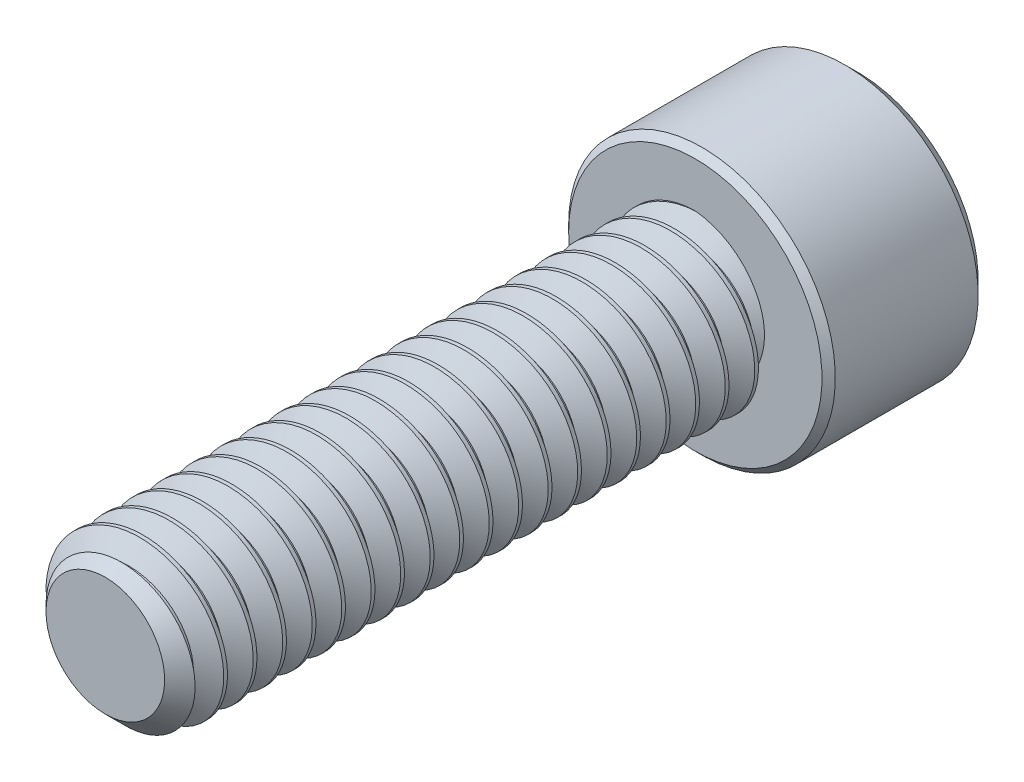
SolidWorks part; units mm, degrees
ref_plane "Front Plane" through (0, 0, 0) normal (0, 0, 1) x (1, 0, 0)
ref_plane "Top Plane" through (0, 0, 0) normal (0, 1, 0) x (1, 0, 0)
ref_plane "Right Plane" through (0, 0, 0) normal (1, 0, 0) x (0, 0, -1)
sketch "Sketch0" plane through (0, 0, 0) normal (1, 0, 0) x (0, 0, -1)
  line L0 (0, 0) -> (12.7, 0) construction
  point P2 (16.2052, 0)
  point P4 (0, 0)
  dimension "D1" = 12.7
  dimension "D2" = 3.5052
  dimension "Min Thread" = 0
sketch "Sketch1" plane through (0, 0, 0) normal (0, 0, 1) x (1, 0, 0)
  circle A0 centre (0, 0) radius 1.7526
  dimension "OD" = 3.5052
extrude "Extrude1" add sketch "Sketch1" against normal blind 12.7
sketch "Sketch2" plane through (0, 0, 0) normal (0, 0, 1) x (1, 0, 0)
  circle A0 centre (0, 0) radius 1.7526 construction
  circle A1 centre (0, 0) radius 1.7526
curve "Helix/Spiral1" pitch 0.635 height 13.335 turns 21 parameters "pitch"=0.635
chamfer "Chamfer3" distance 0.4763 angle 45 1 edges at (1.7526, 0, 0)
sketch "Sketch3" plane through (0, 0, 0) normal (1, 0, 0) x (0, 0, -1)
  line L0 (-0.5556, 1.7526) -> (-0.3175, 1.3402)
  line L1 (-0.3175, 1.3402) -> (-0.2381, 1.3402)
  line L2 (-0.2381, 1.3402) -> (0, 1.7526)
  line L3 (-0.5556, 1.7526) -> (0, 1.7526)
  line L4 (-0.2778, 1.7526) -> (-0.2778, 1.3402) construction
  line L5 (-0.4366, 1.5464) -> (-0.1191, 1.5464) construction
  line L6 (0, 1.7526) -> (0, -1.7526) construction
  dimension "D1" = 0.0794
  dimension "D2" = 0.3175
  dimension "D3" = 60
sweep "Cut-Sweep1" cut profiles "Sketch3" path "Helix/Spiral1"
sketch "Sketch5" plane through (0, 0, 0) normal (1, 0, 0) x (0, 0, -1)
  line L0 (12.7, -1.35) -> (12.7, 1.2505) construction
  line L1 (12.7, 1.7526) -> (0, 1.7526)
  line L2 (12.7, 1.7526) -> (12.7, 0)
  line L3 (12.7, 0) -> (-0.6379, 0)
  line L4 (0, 0) -> (12.7, 0) construction
  line L5 (0, 1.7526) -> (-0.6379, 0)
  line L6 (0, 0) -> (15.24, 0) construction
  dimension "D1" = 70
  dimension "D3" = 2.54
revolve "partially thread" [suppressed] add sketch "Sketch5" angle 360 about L6
sketch "Sketch6" plane through (0, 0, -12.7) normal (0, 0, -1) x (-1, 0, 0)
  circle A0 centre (0, 0) radius 2.8702
  dimension "head dia" = 5.7404
extrude "Extrude2" add sketch "Sketch6" along normal blind 3.5052
sketch "Sketch7" plane through (0, 0, -16.2052) normal (0, 0, -1) x (-1, 0, 0)
  line L1 (0, 1.604) -> (-1.3891, 0.802)
  line L2 (-1.3891, 0.802) -> (-1.3891, -0.802)
  line L3 (-1.3891, -0.802) -> (0, -1.604)
  line L4 (0, -1.604) -> (1.3891, -0.802)
  line L5 (1.3891, -0.802) -> (1.3891, 0.802)
  line L6 (1.3891, 0.802) -> (0, 1.604)
  circle A0 centre (0, 0) radius 1.3891 construction
  dimension "hex dia" = 2.7781
extrude "Cut-Extrude1" cut sketch "Sketch7" against normal blind 2.0836
sketch "Sketch8" plane through (0, 0, -16.2052) normal (0, 0, -1) x (-1, 0, 0)
  circle A0 centre (0, 0) radius 1.604
extrude "Cut-Extrude2" cut sketch "Sketch8" against normal through all draft 45
chamfer "Chamfer1" distance 0.287 angle 45 1 edges at (-2.8702, 0, -16.2052)
chamfer "Chamfer2" distance 0.1435 angle 45 1 edges at (-2.8702, 0, -12.7)
sketch "Sketch9" plane through (0, 0, 0) normal (1, 0, 0) x (0, 0, -1)
  line L0 (0, 1.7526) -> (0, -1.7526) construction
  line L1 (1.5875, 1.7526) -> (1.5875, -1.7526) construction
  line L2 (16.2052, 2.8702) -> (16.2052, -2.8702) construction
  line L3 (12.7, 2.8702) -> (12.7, -2.8702) construction
  line L4 (12.7, 2.7267) -> (12.7, -2.7267) construction
  line L5 (16.2052, -2.5832) -> (16.2052, 2.5832) construction
  line L6 (12.7, -2.8702) -> (12.7, 2.8702) construction
  line L7 (0, 1.2764) -> (0, -1.2764) construction
  line L8 (-0.5556, 1.7526) -> (0, 1.7526) construction
  line L9 (1.5875, 0) -> (0, 0) construction
  dimension "D1" = 1.5875
equation "\"D3@Helix/Spiral1\" = \"screw length@Extrude1\"+\"pitch@Helix/Spiral1\""
equation "\"D1@Sketch3\" = \"pitch@Helix/Spiral1\"*.125"
equation "\"D2@Sketch3\" = \"pitch@Helix/Spiral1\"*.5"
equation "\"D1@Cut-Extrude1\" = \"hex dia@Sketch7\"*.75"
equation "\"D1@Chamfer1\" = \"head dia@Sketch6\"*.05"
equation "\"D1@Sketch9\" = \"pitch@Helix/Spiral1\"*2.50"
equation "\"D1@Chamfer2\" = \"D1@Chamfer1\"/2"
equation "\"D1@Chamfer3\" = \"pitch@Helix/Spiral1\"*.750"
equation "\"D1@Sketch0\" = \"screw length@Extrude1\""
equation "\"D2@Sketch0\" = \"head depth@Extrude2\""
